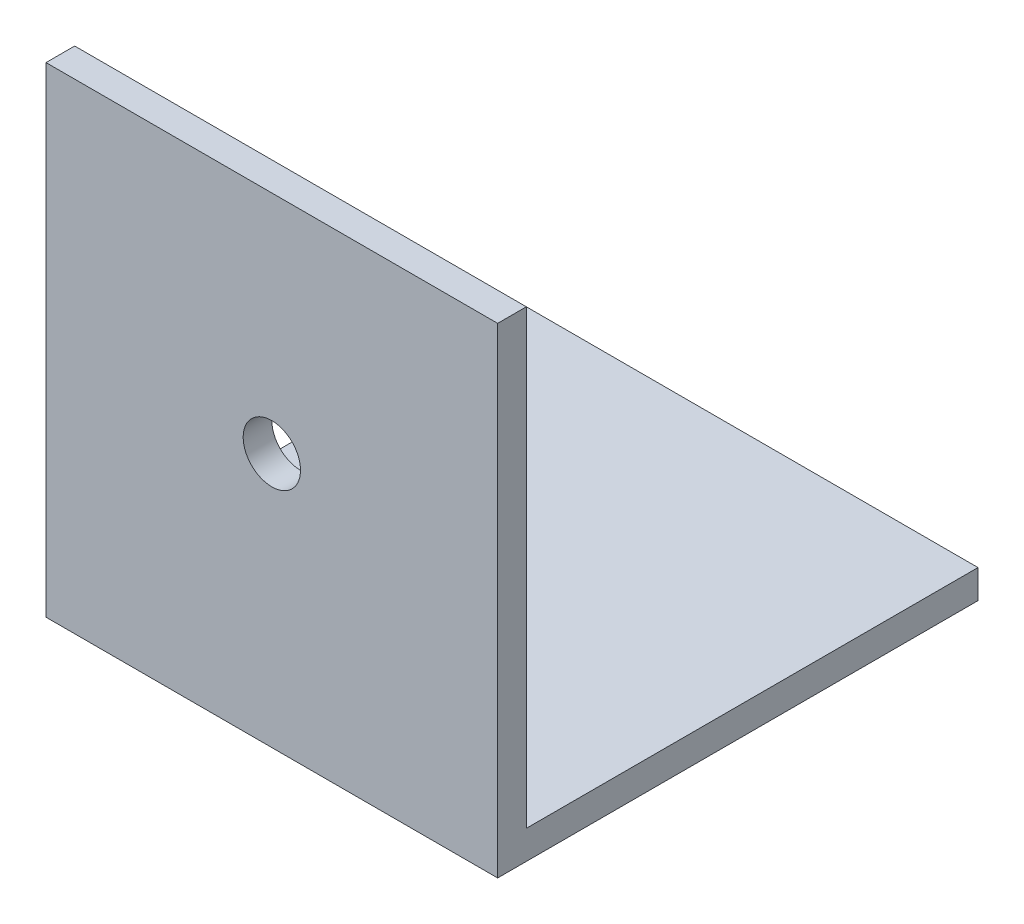
SolidWorks part; units mm, degrees
ref_plane "Front Plane" through (0, 0, 0) normal (0, 0, 1) x (1, 0, 0)
ref_plane "Top Plane" through (0, 0, 0) normal (0, 1, 0) x (1, 0, 0)
ref_plane "Right Plane" through (0, 0, 0) normal (1, 0, 0) x (0, 0, -1)
sketch "Sketch1" plane through (0, 0, 0) normal (1, 0, 0) x (0, 0, -1)
  line L0 (0, 0) -> (0, 100)
  line L1 (0, 100) -> (-6.35, 100)
  line L2 (-6.35, 100) -> (-6.35, -6.35)
  line L3 (-6.35, -6.35) -> (100, -6.35)
  line L4 (100, -6.35) -> (100, 0)
  line L5 (100, 0) -> (0, 0)
  dimension "D1" = 6.35
  dimension "D2" = 6.35
  dimension "D3" = 100
  dimension "D4" = 100
extrude "Boss-Extrude1" add sketch "Sketch1" along normal blind 50 and the other way blind 50
sketch "Sketch2" plane through (0, 0, 0) normal (0, 0, 1) x (1, 0, 0)
  line L0 (0, 0) -> (0, 50) construction
  circle A0 centre (0, 50) radius 6.35
  dimension "D1" = 12.7
  dimension "D2" = 50
extrude "Cut-Extrude1" cut sketch "Sketch2" against normal blind 50 and the other way blind 50
